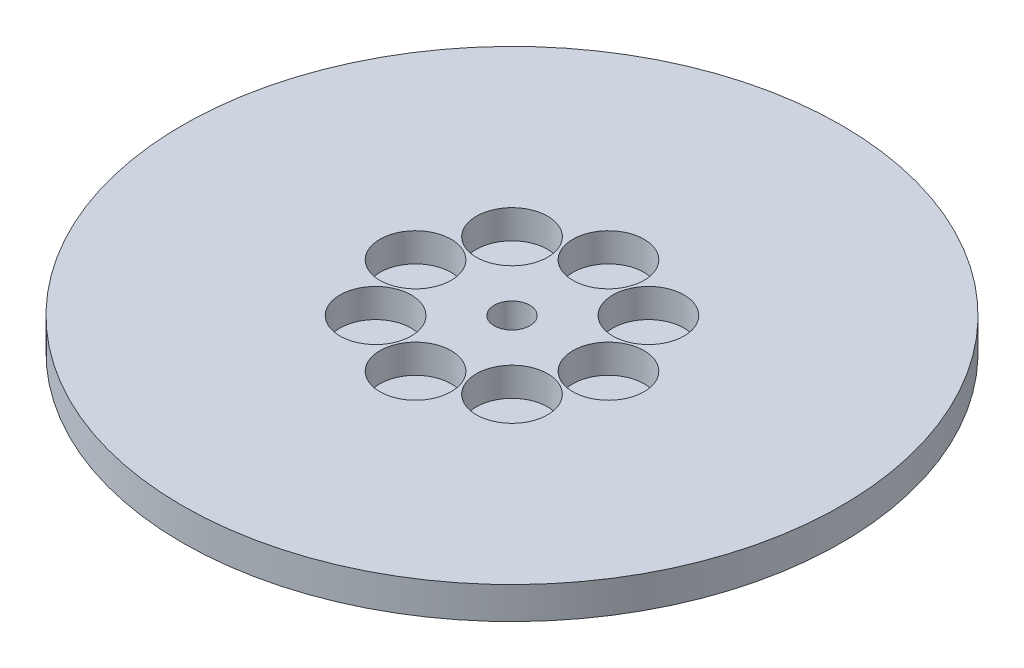
SolidWorks part; units mm, degrees
ref_plane "Front Plane" through (0, 0, 0) normal (0, 0, 1) x (1, 0, 0)
ref_plane "Top Plane" through (0, 0, 0) normal (0, 1, 0) x (1, 0, 0)
ref_plane "Right Plane" through (0, 0, 0) normal (1, 0, 0) x (0, 0, -1)
sketch "Sketch1" plane through (0, 0, 0) normal (0, 1, 0) x (1, 0, 0)
  circle A0 centre (0, 0) radius 92.5
  dimension "FLANGE_OD" = 185
extrude "Boss-Extrude1" add sketch "Sketch1" along normal blind 9
sketch "Sketch2" plane through (0, 0, 0) normal (0, 1, 0) x (1, 0, 0)
  circle A0 centre (0, 0) radius 5
  dimension "BORE_D" = 10
extrude "Cut-Extrude1" cut sketch "Sketch2" along normal through all
sketch "Sketch3" plane through (0, 9, 0) normal (0, 1, 0) x (1, 0, 0)
  circle A0 centre (0, 0) radius 27.0764 construction
  circle A1 centre (-27.0764, 0) radius 10
  dimension "BOLT_D" = 20
  dimension "BOLT_PCD" = 54.1528
extrude "Cut-Extrude2" cut sketch "Sketch3" against normal blind 8.0642
pattern_circular "CirPattern1" count 8 over 360 about axis through (0, 0, 0) along (0, 1, 0) of "Cut-Extrude2"
